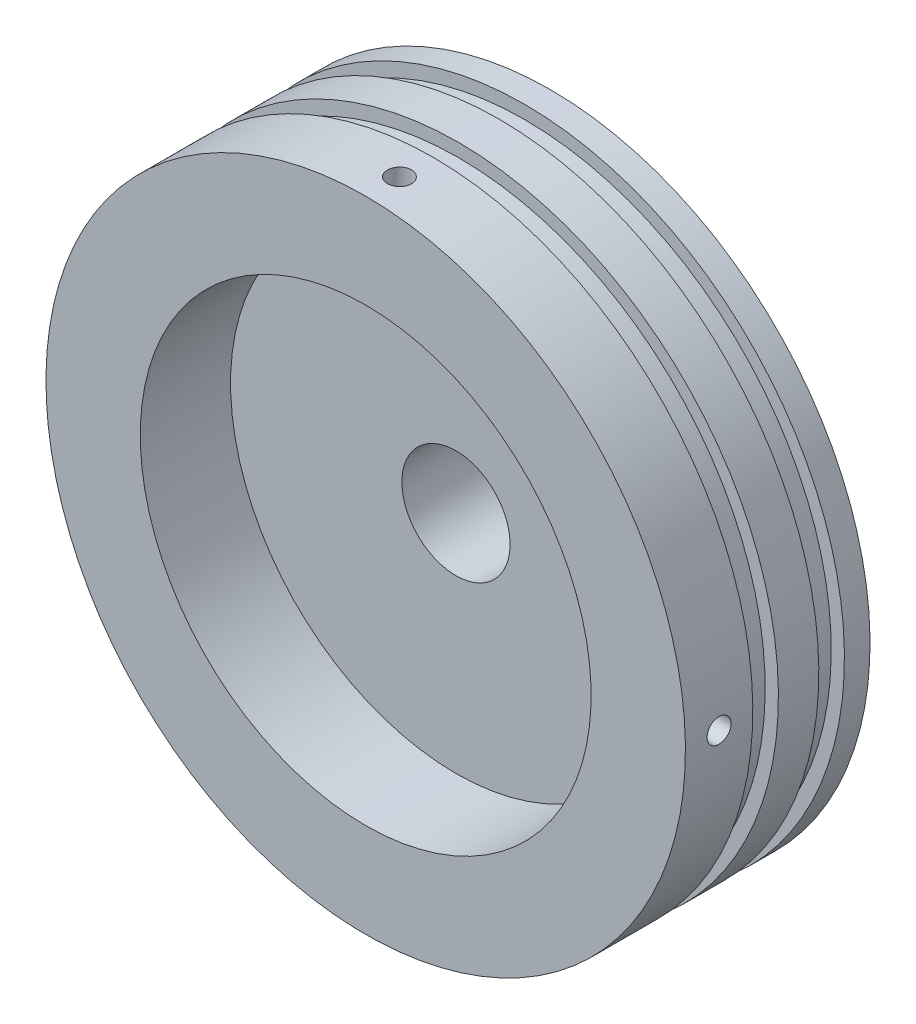
SolidWorks part; units mm, degrees
material "6061-T6 (SS)"
ref_plane "XY" through (0, 0, 0) normal (0, 0, 1) x (1, 0, 0)
ref_plane "XZ" through (0, 0, 0) normal (0, 1, 0) x (1, 0, 0)
ref_plane "YZ" through (0, 0, 0) normal (1, 0, 0) x (0, 0, -1)
ref_axis "X" through (-33.1508, 0, 0) along (1, 0, 0)
ref_axis "Y" through (0, -33.1508, 0) along (0, 1, 0)
ref_axis "Z" through (0, 0, 18.269) along (0, 0, -1)
sketch "Sketch2" plane through (0, 0, 0) normal (1, 0, 0) x (0, 0, -1)
  line L2 (-17.399, 30.1371) -> (-11.049, 30.1371)
  line L3 (-11.049, 30.1371) -> (-11.049, 28.8925)
  line L4 (-11.049, 28.8925) -> (-8.636, 28.8925)
  line L5 (-8.636, 28.8925) -> (-8.636, 30.1371)
  line L6 (-8.636, 30.1371) -> (-4.826, 30.1371)
  line L7 (-4.826, 30.1371) -> (-4.826, 28.8925)
  line L8 (-4.826, 28.8925) -> (-2.413, 28.8925)
  line L9 (-2.413, 28.8925) -> (-2.413, 30.1371)
  line L10 (-2.413, 30.1371) -> (0, 30.1371)
  line L11 (0, 30.1371) -> (0, 0)
  line L12 (0, 0) -> (-8.89, 0)
  line L13 (-17.399, 30.1371) -> (-17.399, 21.2471)
  line L14 (-17.399, 21.2471) -> (-8.89, 21.2471)
  line L15 (-8.89, 21.2471) -> (-8.89, 0)
  dimension "D1" = 30.1371
  dimension "D2" = 28.8925
  dimension "D3" = 2.413
  dimension "D4" = 3.81
  dimension "D5" = 2.413
  dimension "D6" = 8.89
  dimension "D7" = 6.35
revolve "Revolve1" add sketch "Sketch2" angle 360 about L12
hole_wizard "#4-40 Tapped Hole1" positions "3DSketch1" profile "Sketch3" tap size "#4-40" standard "ANSI Inch"
sketch3d "3DSketch1"
  line L0 (0, 0, 0) -> (0, 0, 14.224)
  line L1 (0, 0, 14.224) -> (-30.1371, 0, 14.224)
  line L3 (30.1371, 0, 14.224) -> (0, -30.1371, 14.224)
  line L5 (0, -30.1371, 14.224) -> (-30.1371, 0, 14.224)
  line L9 (0, 0, 14.224) -> (0, -30.1371, 14.224)
  line L11 (0, 0, 14.224) -> (30.1371, 0, 14.224)
  line L13 (0, 0, 14.224) -> (0, 30.1371, 14.224)
  line L15 (0, -30.1371, 11.049) -> (0, -30.1371, 17.399)
  line L16 (0, 30.1371, 14.224) -> (-30.1371, 0, 14.224)
  line L18 (30.1371, 0, 14.224) -> (0, 30.1371, 14.224)
  circle A1 centre (0, 0, 11.049) radius 30.1371 construction
  circle A2 centre (0, 0, 17.399) radius 30.1371 construction
  point P5 (0, -30.1371, 14.224)
  point P7 (30.1371, 0, 14.224)
  point P20 (-30.1371, 0, 14.224)
  point P1370 (0, 0, -19.0881)
  point P1373 (0, 0, -12.7381)
  point P1390 (0, 30.1371, 14.224)
cosmetic thread "Hole Thread2"
cosmetic thread "Hole Thread3"
cosmetic thread "Hole Thread5"
cosmetic thread "Hole Thread6"
sketch "Sketch3" plane through (0, -30.1371, 14.224) normal (1, 0, 0) x (0, 0, -1)
  line L0 (0, 0) -> (0, 8.2992)
  line L1 (0, 8.2992) -> (1.1303, 7.62)
  line L2 (1.1303, 7.62) -> (1.1303, 0)
  line L5 (1.1303, 0) -> (0, 0)
  line L10 (0, 8.2992) -> (-1.1303, 7.62) construction
  line L11 (0, -6.35) -> (0, 107.95) construction
  dimension "Tap Drill Dia." = 2.2606
  dimension "Tap Drill Depth" = 7.62
  dimension "Drill Angle" = 118
hole_wizard "Ø10.2 (10.2) Diameter Hole1" positions "Sketch4" profile "Sketch5" hole size "Ø10.2" standard "ANSI Metric" end condition through all
sketch "Sketch4" plane through (0, 0, 8.89) normal (0, 0, 1) x (1, 0, 0)
  point P0 (0, 0)
sketch "Sketch5" plane through (0, 0, 8.89) normal (1, 0, 0) x (0, -1, 0)
  line L0 (0, 0) -> (0, 8.89)
  line L1 (0, 8.89) -> (5.1, 8.89)
  line L2 (5.1, 8.89) -> (5.1, 0)
  line L5 (5.1, 0) -> (0, 0)
  line L11 (0, -6.35) -> (0, 107.95) construction
  dimension "Thru Hole Dia." = 10.2
  dimension "Thru Hole Depth" = 8.89
